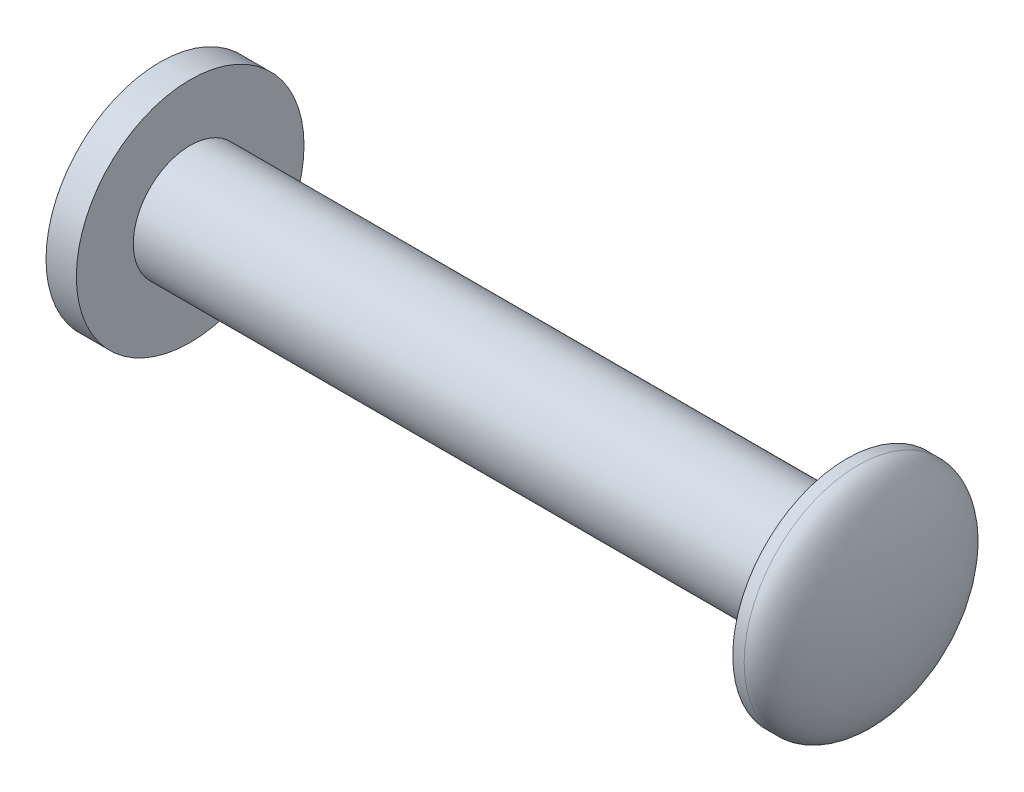
SolidWorks part; units mm, degrees
ref_plane "Alzado" through (0, 0, 0) normal (0, 0, 1) x (1, 0, 0)
ref_plane "Planta" through (0, 0, 0) normal (0, 1, 0) x (1, 0, 0)
ref_plane "Vista lateral" through (0, 0, 0) normal (1, 0, 0) x (0, 0, -1)
sketch "Croquis1" plane through (0, 0, 0) normal (1, 0, 0) x (0, 0, -1)
  circle A0 centre (0, 0) radius 3
  dimension "D1" = 6
extrude "Saliente-Extruir1" add sketch "Croquis1" along normal blind 0.8
sketch "Croquis2" plane through (0.8, 0, 0) normal (1, 0, 0) x (0, 0, -1)
  circle A0 centre (0, 0) radius 1.5
extrude "Saliente-Extruir2" add sketch "Croquis2" along normal blind 17.3
sketch "Croquis3" plane through (18.1, 0, 0) normal (1, 0, 0) x (0, 0, -1)
  circle A0 centre (0, 0) radius 3 construction
  circle A1 centre (0, 0) radius 3
extrude "Saliente-Extruir3" add sketch "Croquis3" along normal blind 0.3
dome "Cúpula1" faces to dome 1 distance 1 reverse direction no elliptical dome yes face at (18.4, 0, -3) parameters "D1"=1
